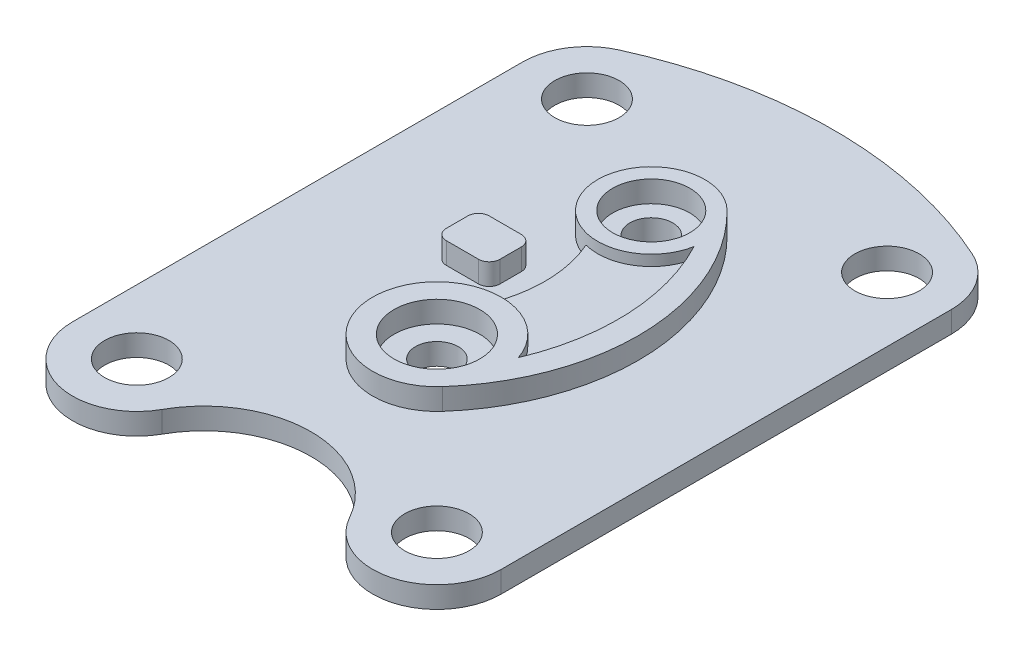
SolidWorks part; units mm, degrees
ref_plane "Front Plane" through (0, 0, 0) normal (0, 0, 1) x (1, 0, 0)
ref_plane "Top Plane" through (0, 0, 0) normal (0, 1, 0) x (1, 0, 0)
ref_plane "Right Plane" through (0, 0, 0) normal (1, 0, 0) x (0, 0, -1)
sketch "Sketch1" plane through (0, 0, 0) normal (0, 1, 0) x (1, 0, 0)
  line L0 (-100, 105) -> (-100, -105)
  line L1 (70, 105) -> (-70, 105)
  line L2 (70, 105) -> (70, -105)
  line L3 (70, -105) -> (-70, -105)
  line L4 (-70, 105) -> (-70, -105)
  line L5 (70, 105) -> (-70, -105) construction
  line L6 (70, -105) -> (-70, 105) construction
  line L7 (0, 0) -> (23.115, 0) construction
  line L8 (23.115, 0) -> (0, 0) construction
  line L9 (0, 0) -> (0, 21.3914) construction
  line L10 (100, 105) -> (100, -105)
  line L11 (-70, 15) -> (70, 15) construction
  line L14 (-35.5892, 5) -> (-20.5892, 5)
  line L15 (-40.5892, 10) -> (-40.5892, 20)
  line L16 (-35.5892, 25) -> (-20.5892, 25)
  line L17 (-15.5892, 10) -> (-15.5892, 20)
  line L18 (-40.5892, 5) -> (-15.5892, 25) construction
  line L19 (-40.5892, 25) -> (-15.5892, 5) construction
  circle A0 centre (-70, -105) radius 15
  circle A1 centre (-70, -105) radius 30
  circle A2 centre (70, -105) radius 15
  circle A3 centre (70, -105) radius 30
  circle A4 centre (70, 105) radius 15
  circle A5 centre (70, 105) radius 30
  circle A6 centre (-70, 105) radius 15
  circle A7 centre (-70, 105) radius 30
  arc A8 (43.75, -119.5237) -> (-43.75, -119.5237) centre (0, -143.7298) ccw
  arc A10 (82.3529, 132.3387) -> (-82.3529, 132.3387) centre (0, -49.9193) ccw
  circle A11 centre (0, -35) radius 10
  circle A12 centre (0, -35) radius 20
  circle A13 centre (0, -35) radius 30
  circle A17 centre (0, 65) radius 10
  circle A18 centre (0, 65) radius 18
  circle A19 centre (0, 65) radius 25
  arc A22 (13.9858, 76.3312) -> (15.9283, -47.095) centre (-63.7132, 13.38) cw
  arc A23 (-14.1119, 53.8262) -> (-15.2879, -22.105) centre (-61.1515, 16.58) cw
  arc A24 (-22.4719, -54.875) -> (-17.4781, 82.875) centre (52.4343, 11.375) cw
  arc A25 (22.4719, -54.875) -> (17.4781, 82.875) centre (-52.4343, 11.375) ccw
  arc A26 (-20.5892, 5) -> (-15.5892, 10) centre (-20.5892, 10) ccw
  arc A27 (-35.5892, 5) -> (-40.5892, 10) centre (-35.5892, 10) cw
  arc A28 (-20.5892, 25) -> (-15.5892, 20) centre (-20.5892, 20) cw
  arc A29 (-40.5892, 20) -> (-35.5892, 25) centre (-35.5892, 20) cw
  point P0 (0, 0)
  point P49 (-28.0892, 15)
  dimension "D3" = 30
  dimension "D4" = 60
  dimension "D7" = 100
  dimension "D8" = 400
  dimension "D9" = 20
  dimension "D10" = 40
  dimension "D11" = 60
  dimension "D14" = 50
  dimension "D15" = 36
  dimension "D16" = 20
  dimension "D18" = 60
  dimension "D19" = 100
  dimension "D20" = 100
  dimension "D21" = 100
  dimension "D24" = 5
  dimension "D1" = 210
  dimension "D2" = 140
  dimension "D12" = 90
  dimension "D13" = 50
  dimension "D17" = 100
  dimension "D22" = 20
  dimension "D23" = 25
  dimension "D5" = 2
  dimension "D6" = 2
extrude "Boss-Extrude1" add sketch "Sketch1" along normal blind 10 contours A7 L0 A1 L4 | L4 A1 L3 A0 | A8 L3 A3 L2 A5 L1 A7 L4 A1 A25 A13 A24 A19 | L3 A1 L4 A0 | A8 L3 A1 | A8 A3 L3 | L2 A3 L3 A2 | A3 L2 A2 L3 | L2 A5 L1 A4 | L1 A5 L2 A4 | L4 A7 L1 A6 | L1 A7 L4 A6 | A18 A17 | A18 A23 A19 A22 | A19 A23 A13 A22 | A13 A23 A12 A22 | A12 A11 | A23 A13 A22 A12 | A23 A18 A22 A19 | A29 L15 A27 L14 A26 L17 A28 L16 | A24 A13 A23 A19 L15 A29 L16 A28 L17 A26 L14 A27 | A13 A25 A19 A22 | A5 L2 A3 L10 | A5 A10 A7 L1 region at (-85.6561, 0, 0) region at (-94.4921, 0, -120.8096) region at (-90.6132, 0, 84.3868) region at (0, 0, -128.2541) region at (-47.0021, 0, -82.0021) region at (-55.1455, 0, -90.1455) region at (-37.8682, 0, 108.6113) region at (-55.1455, 0, 90.1455) region at (94.4921, 0, -120.8096) region at (55.1455, 0, -90.1455) region at (85.6561, 0, 0) region at (37.8682, 0, 108.6113) region at (77.2879, 0, 133.2258) region at (55.1455, 0, 90.1455) region at (-28.0892, 0, -15) region at (18.4186, 0, 41.2005) region at (11.6093, 0, 17.3224) region at (-13.0273, 0, 51.273) region at (17.8364, 0, -17.2646) region at (-29.7196, 0, 24.7007) region at (37.2439, 0, -14.4508) region at (-9.3142, 0, -47.8347) region at (-23.4778, 0, -58.7382) region at (-10.9344, 0, -78.6517)
extrude "Boss-Extrude2" add sketch "Sketch1<3>" along normal blind 20 contours A13 A23 A12 A22 | A23 A13 A22 A12 | A18 A23 A19 A22 | A23 A18 A22 A19 | A29 L15 A27 L14 A26 L17 A28 L16 | A13 A25 A19 A22 region at (-28.0892, 0, -15) region at (11.6093, 0, 17.3224) region at (-13.0273, 0, 51.273) region at (37.2439, 0, -14.4508) region at (-9.3142, 0, -47.8347) region at (-23.4778, 0, -58.7382)
sketch "Sketch1<3>" plane through (0, 0, 0) normal (0, 1, 0) x (1, 0, 0) same geometry as "Sketch1"
extrude "Boss-Extrude3" add sketch "Sketch1<4>" along normal blind 15 contours A19 A23 A13 A22 region at (17.8364, 0, -17.2646)
sketch "Sketch1<4>" plane through (0, 0, 0) normal (0, 1, 0) x (1, 0, 0) same geometry as "Sketch1"
